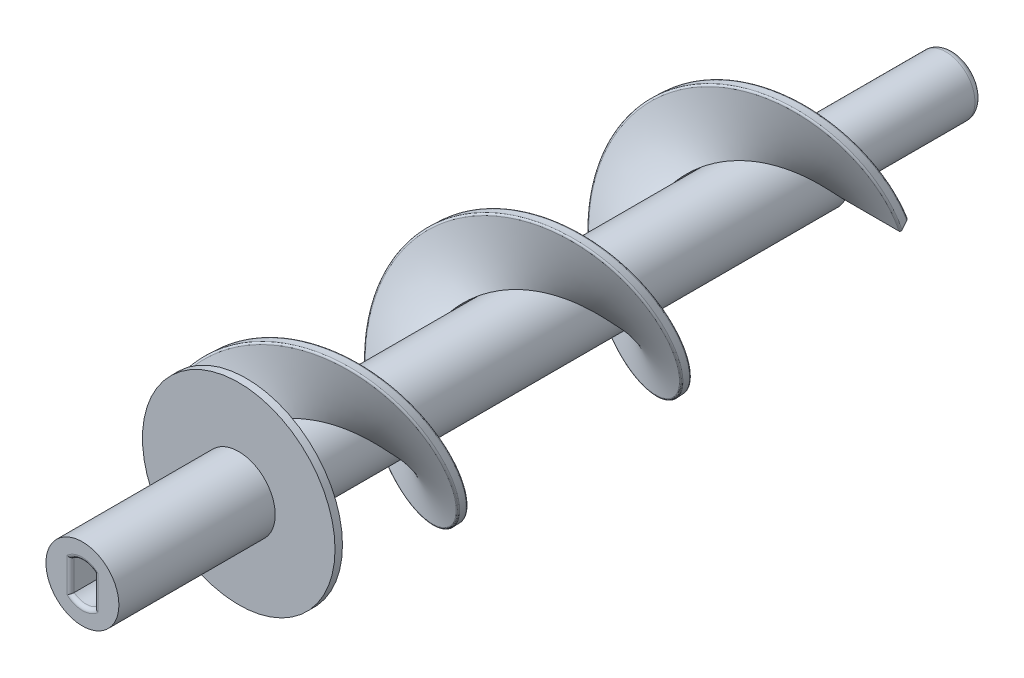
SolidWorks part; units mm, degrees
ref_plane "Front Plane" through (0, 0, 0) normal (0, 0, 1) x (1, 0, 0)
ref_plane "Top Plane" through (0, 0, 0) normal (0, 1, 0) x (1, 0, 0)
ref_plane "Right Plane" through (0, 0, 0) normal (1, 0, 0) x (0, 0, -1)
sketch "Sketch2" plane through (0, 0, 0) normal (0, 0, 1) x (1, 0, 0)
  circle A0 centre (0, 0) radius 4.9
  dimension "D1" = 9.8
extrude "Boss-Extrude1" add sketch "Sketch2" along normal mid plane 98
sketch "Sketch3" plane through (0, 0, -49) normal (0, 0, -1) x (-1, 0, 0)
  circle A0 centre (0, 0) radius 4
curve "Helix/Spiral1" pitch 30 height 75 radius 4 centre (0, 0, -49) axis (0, 0, 1) start towards (1, 0, 0)
ref_plane "Plane1" through (4, 0, -49) normal (0, 0.6422, 0.7666) x (1, 0, 0)
sketch "Sketch5" plane through (4, 0, -49) normal (0, 0.6422, 0.7666) x (1, 0, 0)
  line L1 (0.9, 0) -> (8.65, 0)
  line L2 (0.9, 0) -> (0.9, -1.5)
  line L3 (0.9, -1.5) -> (8.65, -1.5)
  line L4 (8.9, -0.25) -> (8.9, -1.25)
  arc A0 (8.65, -1.5) -> (8.9, -1.25) centre (8.65, -1.25) ccw
  arc A1 (8.65, 0) -> (8.9, -0.25) centre (8.65, -0.25) cw
  ellipse E0 centre (-4, 0) end of major axis (-8.9, 0) minor radius 3.7561 construction
  point P14 (8.9, 0)
  dimension "D3" = 0.25
  dimension "D1" = 8
  dimension "D2" = 1.5
sweep "Sweep1" add profiles "Sketch5" path "Helix/Spiral1"
sketch "Sketch6" plane through (0, 0, 49) normal (0, 0, 1) x (1, 0, 0)
  line L1 (-1.6, -2.0494) -> (1.6, -2.0494)
  line L2 (-1.6, -2.0494) -> (-1.6, 2.0494)
  line L3 (-1.6, 2.0494) -> (1.6, 2.0494)
  line L4 (1.6, -2.0494) -> (1.6, 2.0494)
  line L5 (-1.6, -2.0494) -> (1.6, 2.0494) construction
  line L6 (-1.6, 2.0494) -> (1.6, -2.0494) construction
  circle A0 centre (0, 0) radius 2.6
  dimension "D1" = 5.2
  dimension "D2" = 3.2
extrude "Cut-Extrude1" cut sketch "Sketch6" against normal blind 9 contours L3 A0 | L1 L4 L3 L2 | L1 A0 region at (0, 0, 49) region at (0, -2.2718, 49) region at (0, 2.2718, 49)
sketch "Sketch7" plane through (0, 0, -49) normal (0, 0, -1) x (-1, 0, 0)
  circle A0 centre (0, 0) radius 3.9
  dimension "D1" = 7.8
extrude "Boss-Extrude3" add sketch "Sketch7" along normal blind 19
fillet "Fillet1" radius 1 1 edges at (-3.9, 0, -68)
fillet "Fillet2" radius 0.5 4 edges at (0, -2.6, 49) (1.6, 0, 49) (0, 2.6, 49) (-1.6, 0, 49)
sketch "Sketch8" plane through (0, 0, 49) normal (0, 0, 1) x (1, 0, 0)
  circle A0 centre (0, 0) radius 12.9355
  circle A1 centre (0, 0) radius 4.9
extrude "Boss-Extrude5" add sketch "Sketch8" against normal blind 1 from offset 21 offset against normal yes
